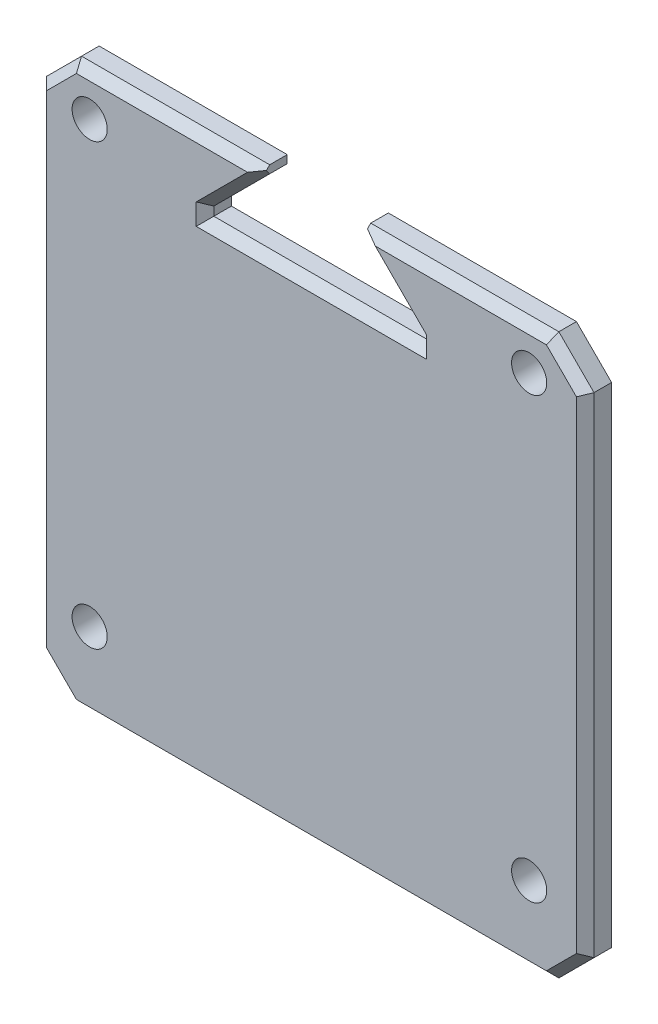
SolidWorks part; units mm, degrees
ref_plane "Front Plane" through (0, 0, 0) normal (0, 0, 1) x (1, 0, 0)
ref_plane "Top Plane" through (0, 0, 0) normal (0, 1, 0) x (1, 0, 0)
ref_plane "Right Plane" through (0, 0, 0) normal (1, 0, 0) x (0, 0, -1)
sketch "Sketch1" plane through (0, 0, 0) normal (0, 0, 1) x (1, 0, 0)
  line L0 (-23.9214, -14.934) -> (-23.9214, -2.684)
  line L1 (-23.9214, -2.684) -> (-24.9214, -1.684)
  line L2 (-24.9214, -1.684) -> (-26.4214, -1.684)
  line L3 (-26.4214, -1.684) -> (-26.4214, 8.316)
  line L4 (-26.4214, 8.316) -> (-24.9214, 8.316)
  line L5 (-24.9214, 8.316) -> (-23.9214, 9.316)
  line L6 (-23.9214, 9.316) -> (-23.9214, 21.566)
  line L7 (-23.9214, 21.566) -> (-18.4214, 27.066)
  line L8 (-18.4214, 27.066) -> (-9.2714, 27.066)
  line L9 (-9.2714, 27.066) -> (-5.2714, 31.066)
  line L10 (-5.2714, 31.066) -> (-5.2714, 32.066)
  line L11 (-5.2714, 32.066) -> (-26.9214, 32.066)
  line L12 (-26.9214, 32.066) -> (-30.9214, 28.066)
  line L13 (-30.9214, 28.066) -> (-30.9214, -27.6088)
  line L14 (-30.9214, -27.6088) -> (-26.9214, -31.6088)
  line L15 (-26.9214, -31.6088) -> (27.3786, -31.6088)
  line L16 (27.3786, -31.6088) -> (31.3786, -27.6088)
  line L17 (31.3786, -27.6088) -> (31.3786, 28.066)
  line L18 (31.3786, 28.066) -> (27.3786, 32.066)
  line L19 (27.3786, 32.066) -> (5.7286, 32.066)
  line L20 (5.7286, 32.066) -> (5.7286, 31.066)
  line L21 (5.7286, 31.066) -> (9.7286, 27.066)
  line L22 (9.7286, 27.066) -> (18.8786, 27.066)
  line L23 (18.8786, 27.066) -> (24.3786, 21.566)
  line L24 (24.3786, 21.566) -> (24.3786, -14.934)
  line L25 (24.3786, -14.934) -> (18.8786, -20.434)
  line L26 (18.8786, -20.434) -> (18.5874, -20.434)
  line L27 (18.5874, -20.434) -> (21.5751, -25.6088)
  line L28 (21.5751, -25.6088) -> (-21.1178, -25.6088)
  line L29 (-21.1178, -25.6088) -> (-18.1301, -20.434)
  line L30 (-18.1301, -20.434) -> (-18.4214, -20.434)
  line L31 (-18.4214, -20.434) -> (-23.9214, -14.934)
sketch "Sketch3" plane through (0, 0, 0) normal (0, 0, 1) x (1, 0, 0)
  line L0 (-26.9214, -31.6088) -> (27.3786, -31.6088) construction
  line L1 (-26.9214, 32.066) -> (27.3786, 32.066)
  line L2 (-30.9214, 28.066) -> (-30.9214, -27.6088)
  line L3 (-26.9214, -31.6088) -> (27.3786, -31.6088)
  line L4 (31.3786, 28.066) -> (31.3786, -27.6088)
  line L7 (-30.9214, 28.066) -> (-26.9214, 32.066)
  line L8 (27.3786, 32.066) -> (31.3786, 28.066)
  line L9 (27.3786, -31.6088) -> (31.3786, -27.6088)
  line L10 (-30.9214, -27.6088) -> (-26.9214, -31.6088)
  line L11 (-5.2714, 32.066) -> (-26.9214, 32.066) construction
  line L12 (31.3786, -27.6088) -> (31.3786, 28.066) construction
  line L13 (-30.9214, 28.066) -> (-30.9214, -27.6088) construction
  point P0 (-30.9214, 32.066)
  point P1 (31.3786, -31.6088)
  point P2 (-30.9214, -31.6088)
  point P3 (31.3786, 32.066)
extrude "Boss-Extrude1" add sketch "Sketch3" along normal blind 3
sketch "Sketch2" plane through (0, 0, 0) normal (0, 0, 1) x (1, 0, 0)
  line L0 (-5.2714, 32.066) -> (-5.2714, 31.066) construction
  line L1 (-5.2714, 31.066) -> (-11.2714, 25.066) construction
  line L2 (-11.2714, 25.066) -> (11.7286, 25.066) construction
  line L3 (11.7286, 25.066) -> (5.7286, 31.066) construction
  line L4 (5.7286, 31.066) -> (5.7286, 32.066) construction
  line L5 (5.7286, 32.066) -> (-5.2714, 32.066) construction
  line L6 (-9.2714, 27.066) -> (-5.2714, 31.066) construction
  line L7 (5.7286, 31.066) -> (9.7286, 27.066) construction
  line L14 (-11.8749, 24.816) -> (-11.8749, 23.816)
  line L15 (-11.8749, 23.816) -> (12.3322, 23.816)
  line L16 (12.3322, 24.816) -> (5.9786, 31.1696)
  line L17 (5.9786, 31.1696) -> (5.9786, 32.316)
  line L18 (5.9786, 32.316) -> (-5.5214, 32.316)
  line L19 (-5.5214, 32.316) -> (-5.5214, 31.1696)
  line L20 (-5.5214, 31.1696) -> (-11.8749, 24.816)
  line L21 (-11.8749, 24.816) -> (12.3322, 24.816) construction
  line L22 (12.3322, 23.816) -> (12.3322, 24.816)
  dimension "D1" = 23
  dimension "D2" = 0.25
  dimension "D3" = 1
extrude "Cut-Extrude4" cut sketch "Sketch2" along normal blind 10 contours L20 L21 L16 L17 L18 L19
sketch "Sketch4" plane through (0, 0, 3) normal (0, 0, 1) x (1, 0, 0)
  line L1 (-975.6214, 3.316) -> (49024.3786, 3.316) construction
  line L3 (24.3786, 21.566) -> (24.3786, -14.934) construction
  circle A0 centre (-25, 27.316) radius 2
  circle A1 centre (25, 27.316) radius 2
  circle A2 centre (25, -22.684) radius 2
  circle A3 centre (-25, -22.684) radius 2
  point P18 (24.3786, 3.316)
  dimension "D3" = 4
  dimension "D6" = 4
  dimension "D7" = 4
  dimension "D8" = 4
  dimension "D1" = 24
  dimension "D2" = 25
  dimension "D4" = 26
  dimension "D5" = 25
chamfer "Chamfer1" distance 1 angle 45 14 edges at (16.6786, 32.066, 3) (29.3786, 30.066, 3) (31.3786, 0.2286, 3) (29.3786, -29.6088, 3) (0.2286, -31.6088, 3) (-28.9214, -29.6088, 3) (-30.9214, 0.2286, 3) (-28.9214, 30.066, 3) (-16.2214, 32.066, 3) (-8.6981, 27.9928, 3) (9.1554, 27.9928, 3) (-11.8749, 24.316, 3) (0.2286, 23.816, 3) (12.3322, 24.316, 3)
extrude "Cut-Extrude5" cut sketch "Sketch4" against normal blind 10
